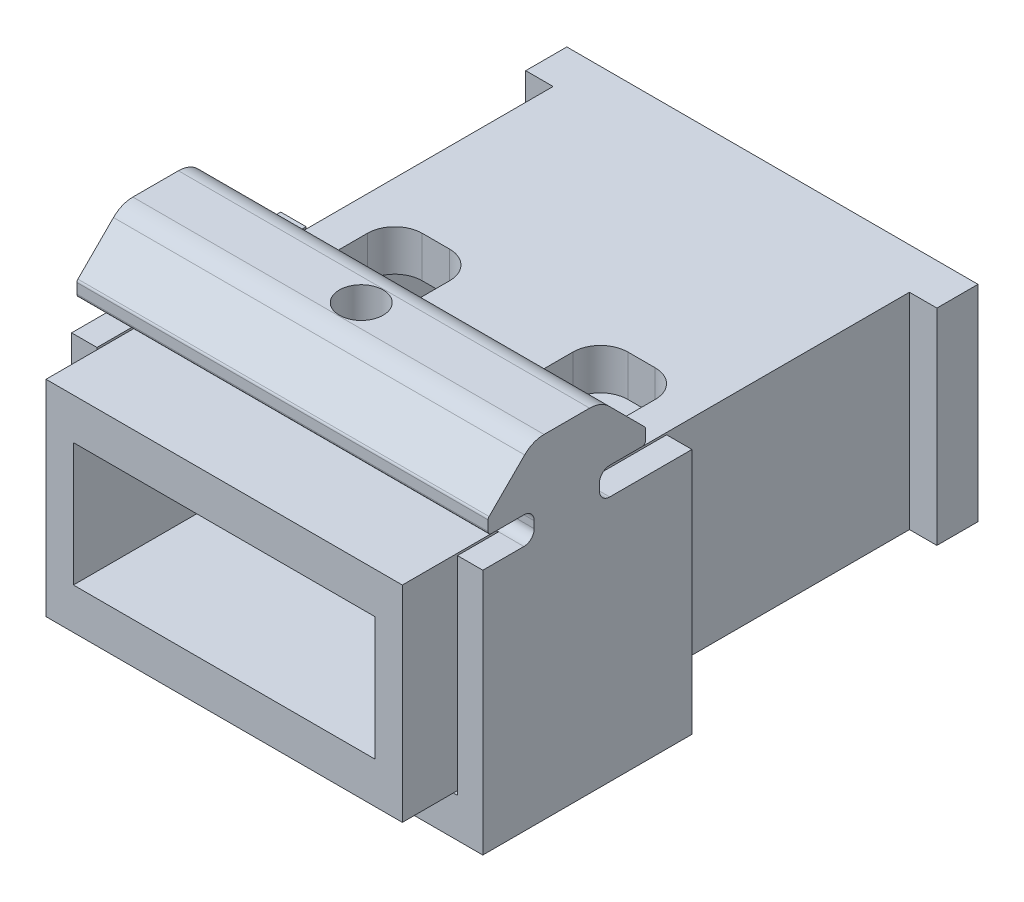
SolidWorks part; units mm, degrees
note: The reader was unsure of these and kept them because the rebuilt part matched: shared geometry of "Sketch13<2>".
ref_plane "Front Plane" through (0, 0, 0) normal (0, 0, 1) x (1, 0, 0)
ref_plane "Top Plane" through (0, 0, 0) normal (0, 1, 0) x (1, 0, 0)
ref_plane "Right Plane" through (0, 0, 0) normal (1, 0, 0) x (0, 0, -1)
sketch "Sketch1" plane through (0, 0, 0) normal (1, 0, 0) x (0, 0, -1)
  line L255 (19.5, -26.25) -> (40, -26.25)
  line L257 (40, -26.25) -> (40, -41.25)
  line L258 (40, -41.25) -> (0, -41.25)
  line L259 (0, -41.25) -> (0, -26.25)
  line L260 (0, -26.25) -> (0.5, -26.25)
  line L266 (13.13, -26.25) -> (19.5, -26.25)
  line L267 (0.5, -26.25) -> (6.87, -26.25)
  line L268 (12.38, -25) -> (12.38, -25.5)
  line L269 (15.495, -24.25) -> (13.13, -24.25)
  line L270 (15.745, -23.2628) -> (15.745, -24)
  line L271 (12.4908, -19.905) -> (15.6718, -23.086)
  line L272 (7.5092, -19.905) -> (12.4908, -19.905)
  line L273 (4.3282, -23.086) -> (7.5092, -19.905)
  line L274 (4.255, -24) -> (4.255, -23.2628)
  line L275 (6.87, -24.25) -> (4.505, -24.25)
  line L276 (7.62, -25.5) -> (7.62, -25)
  line L277 (13.13, -26.25) -> (19.5, -26.25)
  line L278 (0.5, -26.25) -> (6.87, -26.25)
  line L279 (12.38, -25) -> (12.38, -25.5)
  line L280 (15.495, -24.25) -> (13.13, -24.25)
  line L281 (15.745, -23.2628) -> (15.745, -24)
  line L282 (12.4908, -19.905) -> (15.6718, -23.086)
  line L283 (7.5092, -19.905) -> (12.4908, -19.905)
  line L284 (4.3282, -23.086) -> (7.5092, -19.905)
  line L285 (4.255, -24) -> (4.255, -23.2628)
  line L286 (6.87, -24.25) -> (4.505, -24.25)
  line L287 (7.62, -25.5) -> (7.62, -25)
  line L294 (0, -19.13) -> (0, -25.5) construction
  arc A163 (12.38, -25.5) -> (13.13, -26.25) centre (13.13, -25.5) ccw
  arc A164 (6.87, -26.25) -> (7.62, -25.5) centre (6.87, -25.5) ccw
  arc A165 (13.13, -24.25) -> (12.38, -25) centre (13.13, -25) ccw
  arc A166 (15.495, -24.25) -> (15.745, -24) centre (15.495, -24) ccw
  arc A167 (15.745, -23.2628) -> (15.6718, -23.086) centre (15.495, -23.2628) ccw
  arc A168 (4.3282, -23.086) -> (4.255, -23.2628) centre (4.505, -23.2628) ccw
  arc A169 (4.255, -24) -> (4.505, -24.25) centre (4.505, -24) ccw
  arc A170 (7.62, -25) -> (6.87, -24.25) centre (6.87, -25) ccw
  arc A171 (12.38, -25.5) -> (13.13, -26.25) centre (13.13, -25.5) ccw
  arc A172 (6.87, -26.25) -> (7.62, -25.5) centre (6.87, -25.5) ccw
  arc A173 (13.13, -24.25) -> (12.38, -25) centre (13.13, -25) ccw
  arc A174 (15.495, -24.25) -> (15.745, -24) centre (15.495, -24) ccw
  arc A175 (15.745, -23.2628) -> (15.6718, -23.086) centre (15.495, -23.2628) ccw
  arc A176 (4.3282, -23.086) -> (4.255, -23.2628) centre (4.505, -23.2628) ccw
  arc A177 (4.255, -24) -> (4.505, -24.25) centre (4.505, -24) ccw
  arc A178 (7.62, -25) -> (6.87, -24.25) centre (6.87, -25) ccw
  dimension "D2" = 40
  dimension "D3" = 15
  dimension "D1" = 0.25
extrude "Boss-Extrude1" add sketch "Sketch1" along normal mid plane 30
sketch "Sketch2" plane through (0, 0, -40) normal (0, 0, -1) x (-1, 0, 0)
  line L15 (-15, -26.25) -> (15, -26.25) construction
  line L16 (15, -41.25) -> (15, -26.25) construction
  line L22 (11, -38.25) -> (11, -29.25)
  line L23 (-11, -38.25) -> (11, -38.25)
  line L24 (-11, -29.25) -> (-11, -38.25)
  line L25 (11, -29.25) -> (-11, -29.25)
  point P4 (0, -26.25)
  point P5 (0, -29.25)
  point P6 (15, -33.75)
  point P7 (11, -33.75)
  dimension "D1" = 22
  dimension "D2" = 9
extrude "Cut-Extrude1" cut sketch "Sketch2" against normal through all
sketch "Sketch4" plane through (0, -38.25, 0) normal (0, 1, 0) x (1, 0, 0)
  circle A0 centre (-7.5, 19.15) radius 1.2
  circle A1 centre (7.5, 19.15) radius 1.2
  circle A2 centre (-7.5, 19.15) radius 1.4 construction
  circle A3 centre (7.5, 19.15) radius 1.4 construction
  dimension "D1" = 2.4
extrude "Cut-Extrude3" cut sketch "Sketch4" against normal up to surface (3 mm away) up to face at (0, -41.25, -20)
fillet "Fillet1" radius 2 2 edges at (0, -19.905, -12.4908) (0, -19.905, -7.5092)
sketch "Sketch5" plane through (15, 0, 0) normal (1, 0, 0) x (0, 0, -1)
  line L0 (0, -26.25) -> (40, -26.25)
split "Split1" trim tools "Sketch5" bodies to split 104 resulting bodies 105 106
sketch "Sketch3" plane through (0, 0, 0) normal (0, 1, 0) x (1, 0, 0)
  line L0 (-10.5, 20.95) -> (-10.5, 14.95)
  line L3 (10.5, 14.95) -> (10.5, 20.95)
  line L5 (15, 40) -> (15, 0) construction
  line L7 (-4.5, 14.95) -> (-4.5, 20.95)
  line L8 (4.5, 14.95) -> (4.5, 20.95)
  line L9 (-8.5, 12.95) -> (-6.5, 12.95)
  line L10 (6.5, 12.95) -> (8.5, 12.95)
  line L11 (6.5, 22.95) -> (8.5, 22.95)
  line L12 (-8.5, 22.95) -> (-6.5, 22.95)
  line L13 (-10.5, 22.95) -> (10.5, 22.95) construction
  line L14 (7.5, 22.95) -> (7.5, 12.95) construction
  arc A0 (8.5, 12.95) -> (10.5, 14.95) centre (8.5, 14.95) ccw
  arc A1 (-10.5, 14.95) -> (-8.5, 12.95) centre (-8.5, 14.95) ccw
  arc A2 (4.5, 14.95) -> (6.5, 12.95) centre (6.5, 14.95) ccw
  arc A3 (-4.5, 14.95) -> (-6.5, 12.95) centre (-6.5, 14.95) cw
  arc A4 (10.5, 20.95) -> (8.5, 22.95) centre (8.5, 20.95) ccw
  arc A5 (4.5, 20.95) -> (6.5, 22.95) centre (6.5, 20.95) cw
  arc A6 (-4.5, 20.95) -> (-6.5, 22.95) centre (-6.5, 20.95) ccw
  arc A7 (-10.5, 20.95) -> (-8.5, 22.95) centre (-8.5, 20.95) cw
  circle A8 centre (7.5, 19.15) radius 1.2 construction
  point P5 (7.5, 17.95)
  point P12 (0, 22.95)
  point P37 (-4.5, 22.95)
  dimension "D2" = 2
  dimension "D4" = 2
  dimension "D6" = 2
  dimension "D1" = 4.5
  dimension "D3" = 6
  dimension "D5" = 10
extrude "Cut-Extrude2" cut sketch "Sketch3" against normal up to surface (38.25 mm away)
sketch "Sketch6" plane through (0, -19.905, 0) normal (0, 1, 0) x (1, 0, 0)
  line L0 (15, 11.6624) -> (15, 8.3376) construction
  circle A0 centre (0, 10) radius 1.6
  point P4 (15, 10)
  dimension "D1" = 3.2
extrude "Cut-Extrude4" cut sketch "Sketch6" against normal through all
sketch "Sketch10" plane through (0, -41.25, 0) normal (0, -1, 0) x (1, 0, 0)
  line L0 (-15, 0) -> (-15, -40) construction
  line L1 (-15, 0) -> (-13, 0)
  line L2 (-15, 0) -> (-15, -37)
  line L3 (-15, -37) -> (-13, -37)
  line L4 (-13, 0) -> (-13, -37)
  line L5 (15, 0) -> (-15, 0) construction
  line L6 (15, -40) -> (-15, -40) construction
  line L7 (0, 0) -> (0, -40) construction
  line L8 (15, -37) -> (13, -37)
  line L9 (13, 0) -> (13, -37)
  line L10 (15, 0) -> (13, 0)
  line L11 (15, 0) -> (15, -37)
  dimension "D1" = 2
  dimension "D3" = 3
extrude "Cut-Extrude6" cut sketch "Sketch10" against normal up to surface (15 mm away) up to face at (7.5, -26.25, -17.95)
sketch "Sketch11" plane through (0, 0, 0) normal (0, 0, 1) x (1, 0, 0)
  line L0 (-15, -26.25) -> (-15, -44.25)
  line L1 (-15, -44.25) -> (15, -44.25)
  line L2 (15, -44.25) -> (15, -26.25)
  line L3 (15, -26.25) -> (15, -41.25) construction
  line L4 (15, -41.25) -> (-15, -41.25) construction
  line L5 (-15, -26.25) -> (-13, -26.25)
  line L6 (-13, -26.25) -> (-13, -41.25) construction
  line L7 (-13, -41.25) -> (13, -41.25) construction
  line L8 (13, -41.25) -> (13, -26.25) construction
  line L9 (13, -26.25) -> (15, -26.25)
  line L10 (-13.15, -26.25) -> (-13.15, -41.4)
  line L11 (-13.15, -41.4) -> (13.15, -41.4)
  line L12 (13.15, -41.4) -> (13.15, -26.25)
  dimension "D1" = 3
  dimension "D2" = 0.15
extrude "Boss-Extrude2" add sketch "Sketch11" against normal up to vertex (13.13 mm away) from vertex at -6.87 contours L12 L11 L10 L5 L0 L1 L2 L9 starting at point (-15, -26.25, -6.87)
sketch "Sketch13" plane through (0, 0, -6.87) normal (0, 0, 1) x (1, 0, 0)
  line L8 (13.15, -26.25) -> (13.15, -41.4)
  line L9 (13.15, -41.4) -> (-13.15, -41.4)
  line L10 (-13.15, -41.4) -> (-13.15, -26.25)
  line L11 (-13.15, -26.25) -> (-15, -26.25)
  line L12 (-15, -26.25) -> (-15, -44.25)
  line L13 (-15, -44.25) -> (15, -44.25)
  line L14 (15, -44.25) -> (15, -26.25)
  line L15 (15, -26.25) -> (13.15, -26.25)
  line L16 (13.15, -26.25) -> (13.15, -41.4)
  line L17 (13.15, -41.4) -> (-13.15, -41.4)
  line L18 (-13.15, -41.4) -> (-13.15, -26.25)
  line L19 (-13.15, -26.25) -> (-15, -26.25)
  line L20 (-15, -26.25) -> (-15, -44.25)
  line L21 (-15, -44.25) -> (15, -44.25)
  line L22 (15, -44.25) -> (15, -26.25)
  line L23 (15, -26.25) -> (13.15, -26.25)
  dimension "D1" = 0
extrude "Boss-Extrude4" add sketch "Sketch13" along normal blind 3
extrude "Boss-Extrude5" add sketch "Sketch13<2>" against normal blind 6 from surface at -6.26 starting at face at (0, -34.5375, -13.13)
sketch "Sketch13<2>" plane through (0, 0, -6.87) normal (0, 0, 1) x (1, 0, 0) same geometry as "Sketch13"
sketch "Sketch12" plane through (0, -44.25, 0) normal (0, -1, 0) x (1, 0, 0)
  line L1 (-15, -3.87) -> (-15, -11.5) construction
  line L2 (-15, -19.13) -> (-15, -3.87) construction
  line L3 (-15, -11.5) -> (-15, -19.13) construction
  circle A0 centre (0, -7.685) radius 1
  circle A1 centre (0, -15.315) radius 1
  point P6 (-15, -7.685)
  point P17 (-15, -15.315)
  dimension "D1" = 2
extrude "Cut-Extrude7" cut sketch "Sketch12" against normal up to surface (2.85 mm away) up to face at (0, -41.4, -11.5)
